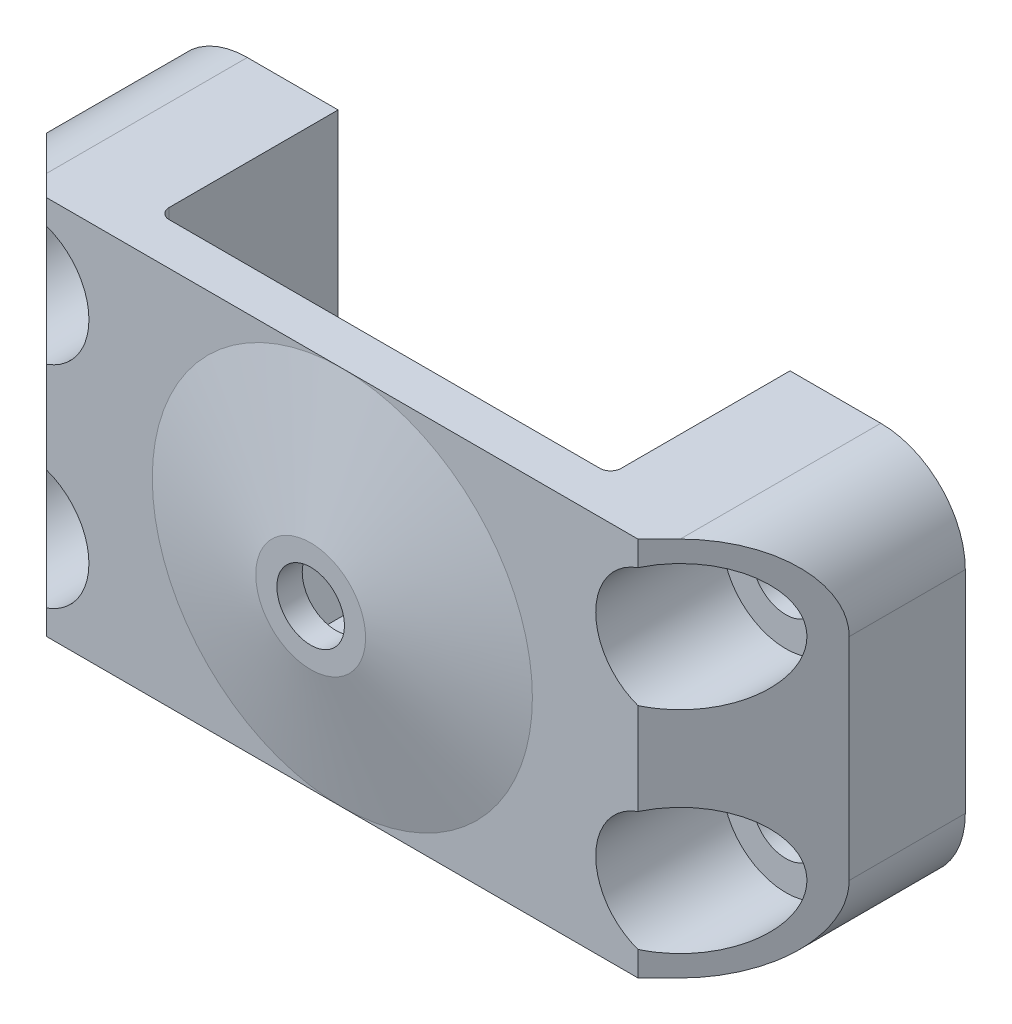
SolidWorks part; units mm, degrees
ref_plane "Front Plane" through (0, 0, 0) normal (0, 0, 1) x (1, 0, 0)
ref_plane "Top Plane" through (0, 0, 0) normal (0, 1, 0) x (1, 0, 0)
ref_plane "Right Plane" through (0, 0, 0) normal (1, 0, 0) x (0, 0, -1)
sketch "Sketch1" plane through (0, 0, 0) normal (0, 1, 0) x (1, 0, 0)
  line L0 (10.7, 10.5) -> (19, 10.5)
  line L1 (-19, 10.5) -> (-10.7, 10.5)
  line L2 (-19, 10.5) -> (-19, 0)
  line L3 (-19, 0) -> (19, 0)
  line L4 (19, 10.5) -> (19, 0)
  line L6 (-10.7, 10.5) -> (-10.7, 2)
  line L7 (-10.7, 2) -> (10.7, 2)
  line L8 (10.7, 10.5) -> (10.7, 2)
  point P7 (0, 2)
  point P9 (0, 0)
  dimension "D1" = 2
  dimension "D2" = 21.4
  dimension "D3" = 38
  dimension "D4" = 8.5
extrude "Boss-Extrude1" add sketch "Sketch1" along normal mid plane 18
sketch "Sketch2" plane through (0, 0, -10.5) normal (0, 0, -1) x (-1, 0, 0)
  line L1 (-15, -5) -> (15, -5) construction
  line L2 (-15, -5) -> (-15, 5) construction
  line L3 (-15, 5) -> (15, 5) construction
  line L4 (15, -5) -> (15, 5) construction
  line L5 (-15, -5) -> (15, 5) construction
  line L6 (-15, 5) -> (15, -5) construction
  circle A0 centre (-15, 5) radius 1.6
  circle A1 centre (-15, -5) radius 1.6
  circle A2 centre (15, 5) radius 1.6
  circle A3 centre (15, -5) radius 1.6
  point P0 (0, 0)
  dimension "D3" = 3.2
  dimension "D1" = 30
  dimension "D2" = 10
extrude "Cut-Extrude1" cut sketch "Sketch2" against normal through all
sketch "Sketch3" plane through (0, 0, -2) normal (0, 0, -1) x (-1, 0, 0)
  circle A0 centre (0, 0) radius 1.6
  dimension "D1" = 3.2
extrude "Cut-Extrude2" cut sketch "Sketch3" against normal through all
sketch "Sketch9" plane through (0, 0, 0) normal (1, 0, 0) x (0, 0, -1)
  line L0 (0, 1.6) -> (0, 9)
  line L1 (0, 9) -> (-1.5, 2.6)
  line L2 (-1.5, 1.6) -> (0, 1.6)
  line L3 (-1.5, 1.6) -> (-1.5, 2.6)
  line L4 (0, 0) -> (-4.1877, 0) construction
  dimension "D1" = 1.5
  dimension "D2" = 1
revolve "Revolve1" add sketch "Sketch9" angle 360 about L4
sketch "Sketch4" plane through (0, 0, -2) normal (0, 0, -1) x (-1, 0, 0)
  line L1 (1.602, 2.8083) -> (-1.6311, 2.7916)
  line L2 (-1.6311, 2.7916) -> (-3.2331, -0.0168)
  line L3 (-3.2331, -0.0168) -> (-1.602, -2.8083)
  line L4 (-1.602, -2.8083) -> (1.6311, -2.7916)
  line L5 (1.6311, -2.7916) -> (3.2331, 0.0168)
  line L6 (3.2331, 0.0168) -> (1.602, 2.8083)
  circle A0 centre (0, 0) radius 2.8 construction
  dimension "D1" = 5.6
extrude "Cut-Extrude3" cut sketch "Sketch4" against normal blind 2.3
sketch "Sketch10" plane through (0, 0, 0) normal (0, 1, 0) x (1, 0, 0)
  line L0 (-19, 0) -> (-19, 5)
  line L1 (-19, 5) -> (-14, 0)
  line L2 (-14, 0) -> (-19, 0)
  line L3 (0, 0) -> (0, 8.4574) construction
  line L4 (14, 0) -> (19, 0)
  line L5 (19, 0) -> (19, 5)
  line L6 (19, 5) -> (14, 0)
  dimension "D1" = 5
extrude "Cut-Extrude4" cut sketch "Sketch10" against normal through all and the other way through all
fillet "Fillet2" radius 4 4 edges at (19, -9, -7.75) (19, 9, -7.75) (-19, -9, -7.75) (-19, 9, -7.75)
fillet "Fillet5" radius 0.5 2 edges at (-10.7, 0, -2) (10.7, 0, -2)
sketch "Sketch11" plane through (0, 0, 0) normal (0, 0, 1) x (1, 0, 0)
  circle A0 centre (-15, 5) radius 3
  circle A1 centre (-15, -5) radius 3
  circle A2 centre (15, 5) radius 3
  circle A3 centre (15, -5) radius 3
  dimension "D1" = 6
extrude "Cut-Extrude5" cut sketch "Sketch11" against normal blind 6
